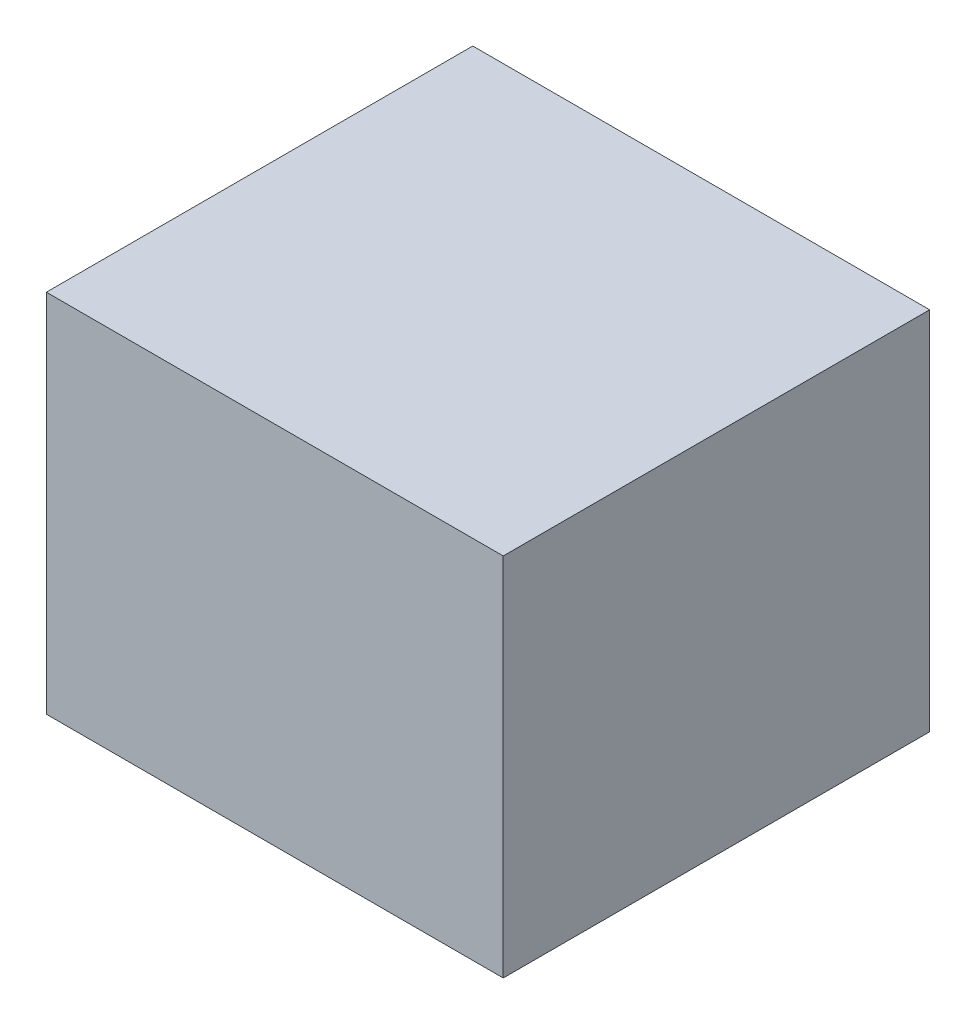
SolidWorks part; units mm, degrees
ref_plane "Ebene vorne" through (0, 0, 0) normal (0, 0, 1) x (1, 0, 0)
ref_plane "Ebene oben" through (0, 0, 0) normal (0, 1, 0) x (1, 0, 0)
ref_plane "Ebene rechts" through (0, 0, 0) normal (1, 0, 0) x (0, 0, -1)
sketch "Skizze1" plane through (0, 0, 0) normal (0, 0, 1) x (1, 0, 0)
  line L1 (0, 0) -> (75, 0)
  line L2 (0, 0) -> (0, 60)
  line L3 (0, 60) -> (75, 60)
  line L4 (75, 0) -> (75, 60)
  dimension "D1" = 75
  dimension "D2" = 60
extrude "Aufsatz-Linear austragen1" add sketch "Skizze1" along normal blind 70
sketch "Skizze4" plane through (0, 0, 0) normal (-1, 0, 0) x (0, 0, 1)
  line L0 (70, 30) -> (-15.3302, 30) construction
  line L1 (70, 60) -> (70, 0) construction
  line L3 (0, 60) -> (0, 0) construction
  line L4 (35, 0) -> (123.5507, 0) construction
  line L6 (35, 0) -> (35, 81.5166) construction
  line L12 (3.35, 56.65) -> (3.35, 3.35)
  line L13 (3.35, 3.35) -> (66.65, 3.35)
  line L14 (66.65, 3.35) -> (66.65, 56.65)
  line L15 (66.65, 56.65) -> (3.35, 56.65)
  dimension "D1" = 53.3
  dimension "D2" = 3.35
  dimension "D3" = 3.35
extrude "Schnitt-Linear austragen1" cut sketch "Skizze4" against normal blind 73
sketch "Skizze7" plane through (0, 0, 70) normal (0, 0, 1) x (1, 0, 0)
  line L2 (0, 60) -> (0, 0)
sketch "Skizze9" plane through (0, 0, 0) normal (-1, 0, 0) x (0, 0, 1)
  line L0 (70, 30) -> (9.2019, 30) construction
  line L1 (3.35, 56.65) -> (3.35, 3.35) construction
  line L2 (66.65, 56.65) -> (3.35, 56.65) construction
  line L3 (11.35, 56.65) -> (8.35, 56.65)
  line L4 (11.35, 56.65) -> (11.35, 55.65)
  line L5 (11.35, 55.65) -> (8.35, 55.65)
  line L6 (8.35, 56.65) -> (8.35, 55.65)
  line L7 (11.35, 4.35) -> (8.35, 4.35)
  line L8 (8.35, 3.35) -> (8.35, 4.35)
  line L9 (11.35, 3.35) -> (8.35, 3.35)
  line L10 (11.35, 3.35) -> (11.35, 4.35)
  dimension "D1" = 1
  dimension "D2" = 3
  dimension "D3" = 5
extrude "Aufsatz-Linear austragen2" add sketch "Skizze9" against normal up to surface (73 mm away) up to face at (73, 30, 35)
